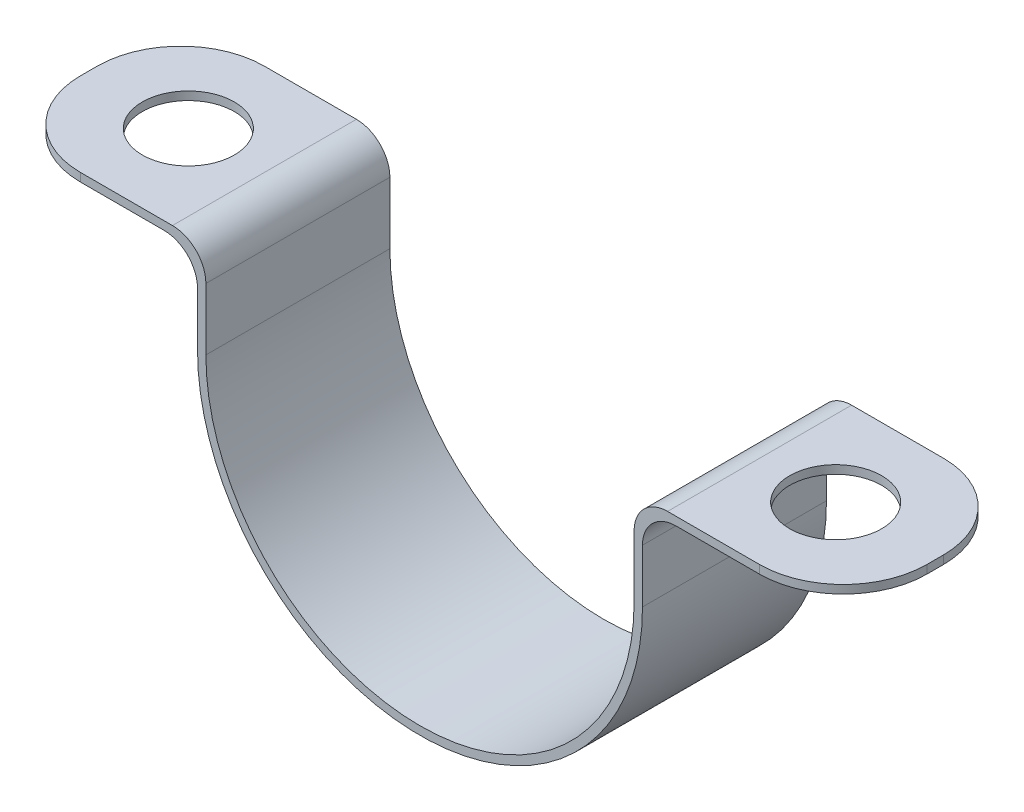
SolidWorks part; units mm, degrees
note: The reader was unsure of these and kept them because the rebuilt part matched: thickness of "Base-Flange1", "Sheet-Metal1", "Sheet-Metal3".
material "AISI 304"
ref_plane "Front Plane" through (0, 0, 0) normal (0, 0, 1) x (1, 0, 0)
ref_plane "Top Plane" through (0, 0, 0) normal (0, 1, 0) x (1, 0, 0)
ref_plane "Right Plane" through (0, 0, 0) normal (1, 0, 0) x (0, 0, -1)
sketch "Sketch1" plane through (0, 0, 0) normal (0, 0, 1) x (1, 0, 0)
  line L9 (-12.8, 0) -> (-12.8, 3.7)
  line L10 (-14.8, 5.7) -> (-25.3, 5.7)
  line L11 (-25.3, 5.7) -> (-25.3, 5.2)
  line L12 (-25.3, 5.2) -> (-15.3, 5.2)
  line L13 (-13.3, 0) -> (-13.3, 3.2)
  line L15 (0, -55) -> (0, 55) construction
  line L16 (25.3, 5.7) -> (25.3, 5.2)
  line L17 (13.3, 0) -> (13.3, 3.2)
  line L18 (12.8, 0) -> (12.8, 3.7)
  line L19 (14.8, 5.7) -> (25.3, 5.7)
  line L20 (25.3, 5.2) -> (15.3, 5.2)
  arc A1 (-13.3, 0) -> (13.3, 0) centre (0, 0) ccw
  arc A2 (-12.8, 0) -> (12.8, 0) centre (0, 0) ccw
  arc A3 (-13.3, 3.2) -> (-15.3, 5.2) centre (-15.3, 3.2) ccw
  arc A4 (-12.8, 3.7) -> (-14.8, 5.7) centre (-14.8, 3.7) ccw
  arc A5 (12.8, 3.7) -> (14.8, 5.7) centre (14.8, 3.7) cw
  arc A6 (13.3, 3.2) -> (15.3, 5.2) centre (15.3, 3.2) cw
  point P18 (-13.3, 5.2)
  point P21 (-12.8, 5.7)
  point P24 (12.8, 5.7)
  point P27 (13.3, 5.2)
  dimension "D1" = 5.7
  dimension "D2" = 2
  dimension "D5" = 2
  dimension "D3" = 0.5
  dimension "D4" = 12.8
  dimension "D8" = 0.5
  dimension "D9" = 12.5
base flange "Base-Flange1" sketch "Sketch1" thickness 11 reverse thickness direction no parameters "D1"=0.7366
sketch "Sketch6" plane through (0, 0, 0) normal (0, 1, 0) x (1, 0, 0)
  line L5 (25.3, 11) -> (25.3, 0) construction
  line L7 (0, -55) -> (0, 55) construction
  circle A7 centre (19.35, 5.5) radius 2.75
  circle A8 centre (-19.35, 5.5) radius 2.75
  point P2 (20.0462, 5.2879)
  point P6 (34.5329, 12.9729)
  dimension "D1" = 5.5
  dimension "D2" = 3.2
  dimension "D3" = 5.5
fillet "Fillet1" radius 5 4 edges at (25.3, 5.45, 0) (25.3, 5.45, -11) (-25.3, 5.45, 0) (-25.3, 5.45, -11)
extrude "Cut-Extrude1" cut sketch "Sketch6" along normal blind 10 contours A7 | A8 normal cut yes
sketch "Bend-Lines1" [suppressed] plane through (0, 0, 0) normal (0, 1, 0) x (1, 0, 0)
sketch "Bounding-Box1" [suppressed] plane through (0, 0, 0) normal (0, 1, 0) x (1, 0, 0)
sheet metal parameters "Sheet-Metal1" thickness 11 parameters "D1"=0.7366
flat pattern "Flat-Pattern1" [suppressed]
sketch "Bend-Lines2" plane through (0, 0, 0) normal (0, 1, 0) x (1, 0, 0)
sketch3d "Bounding-Box2" [suppressed]
  line L0 (-25.3, -14.8, 0) -> (25.3, -14.8, 0) construction
  line L1 (-25.3, 5.7, 0) -> (25.3, 5.7, 0) construction
  line L2 (-25.3, -14.8, 0) -> (-25.3, 5.7, 0) construction
  line L3 (25.3, -14.8, 0) -> (25.3, 5.7, 0) construction
sheet metal parameters "Sheet-Metal3" thickness 11 parameters "D1"=0.7366
flat pattern "Flat-Pattern1"
sketch "Bend-Lines2" plane through (0, 0, 0) normal (0, 1, 0) x (1, 0, 0)
sketch3d "Bounding-Box2" [suppressed]
  line L0 (-25.3, -13.3, 0) -> (25.3, -13.3, 0) construction
  line L1 (-25.3, 5.7, 0) -> (25.3, 5.7, 0) construction
  line L2 (-25.3, -13.3, 0) -> (-25.3, 5.7, 0) construction
  line L3 (25.3, -13.3, 0) -> (25.3, 5.7, 0) construction
